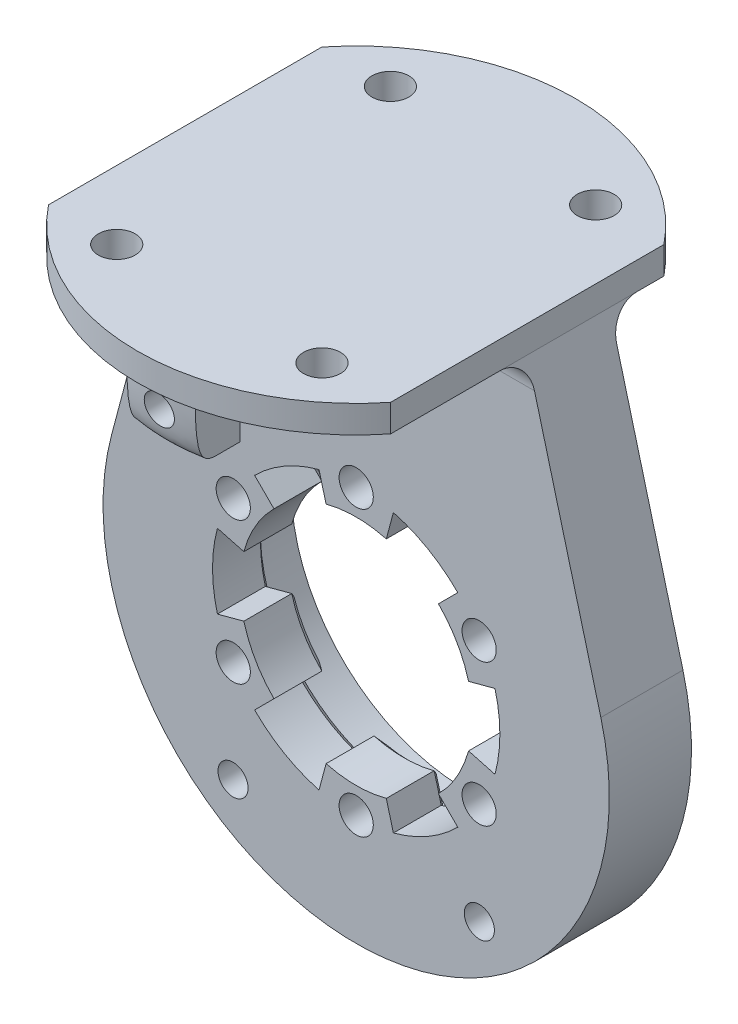
SolidWorks part; units mm, degrees
ref_plane "정면" through (0, 0, 0) normal (0, 0, 1) x (1, 0, 0)
ref_plane "윗면" through (0, 0, 0) normal (0, 1, 0) x (1, 0, 0)
ref_plane "우측면" through (0, 0, 0) normal (1, 0, 0) x (0, 0, -1)
sketch "스케치1" plane through (0, 0, 0) normal (0, 0, 1) x (1, 0, 0)
  line L0 (0, 0) -> (0, 30.9878) construction
  line L1 (12.5, 0) -> (12.5, 25) construction
  line L2 (-12.5, 0) -> (-12.5, 25) construction
  line L3 (-12.5, 25) -> (12.5, 25)
  line L12 (-12.5, 0) -> (12.5, 0) construction
  line L15 (-12.5, 25) -> (-17.8798, 4.7501)
  line L16 (12.5, 25) -> (17.8798, 4.7501)
  line L21 (-12.5, 0) -> (-12.5, 114.0122) construction
  line L22 (0, 0) -> (0, 114.0122) construction
  line L23 (12.5, 0) -> (12.5, 114.0122) construction
  arc A2 (-17.8798, 4.7501) -> (17.8798, 4.7501) centre (0, 0) ccw
  dimension "D1" = 18.5
  dimension "D3" = 25
  dimension "D2" = 25
extrude "보스-돌출1" add sketch "스케치1" along normal blind 6
sketch "스케치4" plane through (0, 0, 0) normal (0, 0, -1) x (-1, 0, 0)
  circle A0 centre (0, 0) radius 12.75
  dimension "D1" = 25.5
extrude "컷-돌출2" cut sketch "스케치4" against normal blind 2
sketch "스케치5" plane through (0, 0, 2) normal (0, 0, -1) x (-1, 0, 0)
  circle A0 centre (0, 0) radius 8.5
  dimension "D1" = 17
extrude "컷-돌출3" cut sketch "스케치5" against normal through all
sketch "스케치6" plane through (0, 0, 0) normal (0, 0, -1) x (-1, 0, 0)
  circle A0 centre (0, 0) radius 12.75
  circle A1 centre (0, 0) radius 13.75
  dimension "D1" = 1
extrude "보스-돌출2" add sketch "스케치6" along normal blind 2
sketch "스케치7" plane through (0, 0, 2) normal (0, 0, -1) x (-1, 0, 0)
  line L1 (2.2, 8.2104) -> (2.7176, 10.1422)
  line L3 (6.0104, 6.0104) -> (7.4246, 7.4246)
  line L5 (8.2104, 2.2) -> (10.1422, 2.7176)
  line L7 (8.2104, -2.2) -> (10.1422, -2.7176)
  line L9 (6.0104, -6.0104) -> (7.4246, -7.4246)
  line L11 (2.2, -8.2104) -> (2.7176, -10.1422)
  line L13 (-2.2, -8.2104) -> (-2.7176, -10.1422)
  line L15 (-6.0104, -6.0104) -> (-7.4246, -7.4246)
  line L17 (-8.2104, -2.2) -> (-10.1422, -2.7176)
  line L19 (-8.2104, 2.2) -> (-10.1422, 2.7176)
  line L21 (-6.0104, 6.0104) -> (-7.4246, 7.4246)
  line L23 (-2.2, 8.2104) -> (-2.7176, 10.1422)
  arc A0 (-2.2, 8.2104) -> (-6.0104, 6.0104) centre (0, 0) ccw
  arc A1 (-2.7176, 10.1422) -> (-7.4246, 7.4246) centre (0, 0) ccw
  circle A2 centre (0, 0) radius 8.5 construction
  circle A3 centre (0, 0) radius 10.5 construction
  arc A4 (6.0104, 6.0104) -> (2.2, 8.2104) centre (0, 0) ccw
  arc A5 (7.4246, 7.4246) -> (2.7176, 10.1422) centre (0, 0) ccw
  arc A6 (8.2104, -2.2) -> (8.2104, 2.2) centre (0, 0) ccw
  arc A7 (10.1422, -2.7176) -> (10.1422, 2.7176) centre (0, 0) ccw
  arc A8 (2.2, -8.2104) -> (6.0104, -6.0104) centre (0, 0) ccw
  arc A9 (2.7176, -10.1422) -> (7.4246, -7.4246) centre (0, 0) ccw
  arc A10 (-6.0104, -6.0104) -> (-2.2, -8.2104) centre (0, 0) ccw
  arc A11 (-7.4246, -7.4246) -> (-2.7176, -10.1422) centre (0, 0) ccw
  arc A12 (-8.2104, 2.2) -> (-8.2104, -2.2) centre (0, 0) ccw
  arc A13 (-10.1422, 2.7176) -> (-10.1422, -2.7176) centre (0, 0) ccw
  point P31 (0, 0)
  dimension "D1" = 2
extrude "컷-돌출4" cut sketch "스케치7" against normal through all
chamfer "모따기1" distance 0.5 angle 45 24 edges at (7.3612, 4.25, 2) (9.1763, 2.4588, 2) (10.5, 0, 2) (9.1763, -2.4588, 2) (7.3612, -4.25, 2) (6.7175, -6.7175, 2) (5.25, -9.0933, 2) (2.4588, -9.1763, 2) (0, -8.5, 2) (-2.4588, -9.1763, 2) (-5.25, -9.0933, 2) (-6.7175, -6.7175, 2) (-7.3612, -4.25, 2) (-9.1763, -2.4588, 2) (-10.5, 0, 2) (-9.1763, 2.4588, 2) (-7.3612, 4.25, 2) (-6.7175, 6.7175, 2) (-5.25, 9.0933, 2) (-2.4588, 9.1763, 2) (0, 8.5, 2) (2.4588, 9.1763, 2) (5.25, 9.0933, 2) (6.7175, 6.7175, 2)
draft "구배1" type of draft neutral plane draft angle 67 faces to draft 1 face at (-13.75, 0, -2) neutral plane through (0, 0, -2) neutral plane normal (0, 0, -1) parameters "D1"=67
sketch "스케치8" plane through (0, 0, 6) normal (0, 0, 1) x (1, 0, 0)
  circle A0 centre (0, 0) radius 10.375 construction
  circle A1 centre (0, 10.375) radius 1.25
  circle A2 centre (8.985, 5.1875) radius 1.25
  circle A3 centre (8.985, -5.1875) radius 1.25
  circle A4 centre (0, -10.375) radius 1.25
  circle A5 centre (-8.985, -5.1875) radius 1.25
  circle A6 centre (-8.985, 5.1875) radius 1.25
  point P17 (0, 0)
  dimension "D1" = 20.75
  dimension "D2" = 2.5
  dimension "D3" = 6
extrude "컷-돌출5" cut sketch "스케치8" against normal through all
sketch "스케치9" plane through (0, 25, 0) normal (0, 1, 0) x (1, 0, 0)
  line L10 (12.5, -6) -> (-12.5, -6) construction
  line L11 (-12.5, 3.9875) -> (-12.5, -15.9875)
  line L12 (12.5, 3.9875) -> (12.5, -15.9875)
  line L13 (-12.5, -6) -> (-12.5, 0) construction
  line L14 (12.5, -6) -> (12.5, 0) construction
  arc A0 (-12.5, -15.9875) -> (12.5, -15.9875) centre (0, -6) ccw
  arc A1 (12.5, 3.9875) -> (-12.5, 3.9875) centre (0, -6) ccw
  dimension "D1" = 32
extrude "보스-돌출3" add sketch "스케치9" along normal blind 2
fillet "필렛1" radius 2 2 edges at (0, 25, 0) (0, 25, 6)
sketch "스케치11" plane through (0, 27, 0) normal (0, 1, 0) x (1, 0, 0)
  line L1 (-7.5, 4) -> (7.5, 4) construction
  line L2 (-7.5, 4) -> (-7.5, -16) construction
  line L3 (-7.5, -16) -> (7.5, -16) construction
  line L4 (7.5, 4) -> (7.5, -16) construction
  line L5 (-7.5, 4) -> (7.5, -16) construction
  line L6 (-7.5, -16) -> (7.5, 4) construction
  circle A0 centre (0, -6) radius 12.5 construction
  arc A1 (12.5, 3.9875) -> (-12.5, 3.9875) centre (0, -6) ccw construction
  circle A2 centre (-7.5, 4) radius 1.35
  circle A3 centre (7.5, 4) radius 1.35
  circle A4 centre (-7.5, -16) radius 1.35
  circle A5 centre (7.5, -16) radius 1.35
  point P16 (0, -6)
  dimension "D1" = 25
  dimension "D3" = 2.7
  dimension "D2" = 15
extrude "컷-돌출6" cut sketch "스케치11" against normal through all
sketch "스케치12" plane through (0, 25, 0) normal (0, -1, 0) x (1, 0, 0)
  line L2 (-2.5, 20.2829) -> (-2.5, 17)
  line L3 (-2.5, 17) -> (2.5, 17)
  line L4 (2.5, 20.2829) -> (2.5, 17)
  line L5 (0.76, 20.4801) -> (2.5, 17) construction
  line L6 (-2.5, 17) -> (-0.76, 20.4801) construction
  arc A0 (12.5, 15.9875) -> (-12.5, 15.9875) centre (0, 6) ccw construction
  arc A3 (11.3281, 15.0512) -> (-11.3281, 15.0512) centre (0, 6) ccw
  arc A4 (2.5, 20.2829) -> (-2.5, 20.2829) centre (0, 6) ccw
  point P0 (0, 22)
  point P9 (0, 0)
  dimension "D1" = 5
  dimension "D2" = 5
  dimension "D4" = 3.2829
  dimension "D3" = 1.5
extrude "보스-돌출4" add sketch "스케치12" along normal blind 5
sketch "스케치13" plane through (0, 0, 17) normal (0, 0, -1) x (-1, 0, 0)
  line L0 (-2.5, 20) -> (2.5, 20) construction
  line L1 (-2.5, 20) -> (-2.5, 25) construction
  circle A0 centre (0, 22.5) radius 1.1
  dimension "D1" = 2.5
  dimension "D2" = 2.5
  dimension "D3" = 2.2
extrude "컷-돌출7" cut sketch "스케치13" against normal blind 5
sketch "스케치14" plane through (0, 0, 6) normal (0, 0, 1) x (1, 0, 0)
  line L0 (-9, -12.6194) -> (9, -12.6194) construction
  circle A0 centre (0, 0) radius 15.5 construction
  circle A1 centre (-9, -12.6194) radius 1.1
  circle A2 centre (9, -12.6194) radius 1.1
  dimension "D1" = 31
  dimension "D2" = 2.2
  dimension "D3" = 18
extrude "컷-돌출8" cut sketch "스케치14" against normal through all
fillet "필렛2" radius 5 1 edges at (0, 20, 20.5) second distance 1.5 conic rho 0.6 first distance on face at (1.0713, 22.2505, 20.4604)
